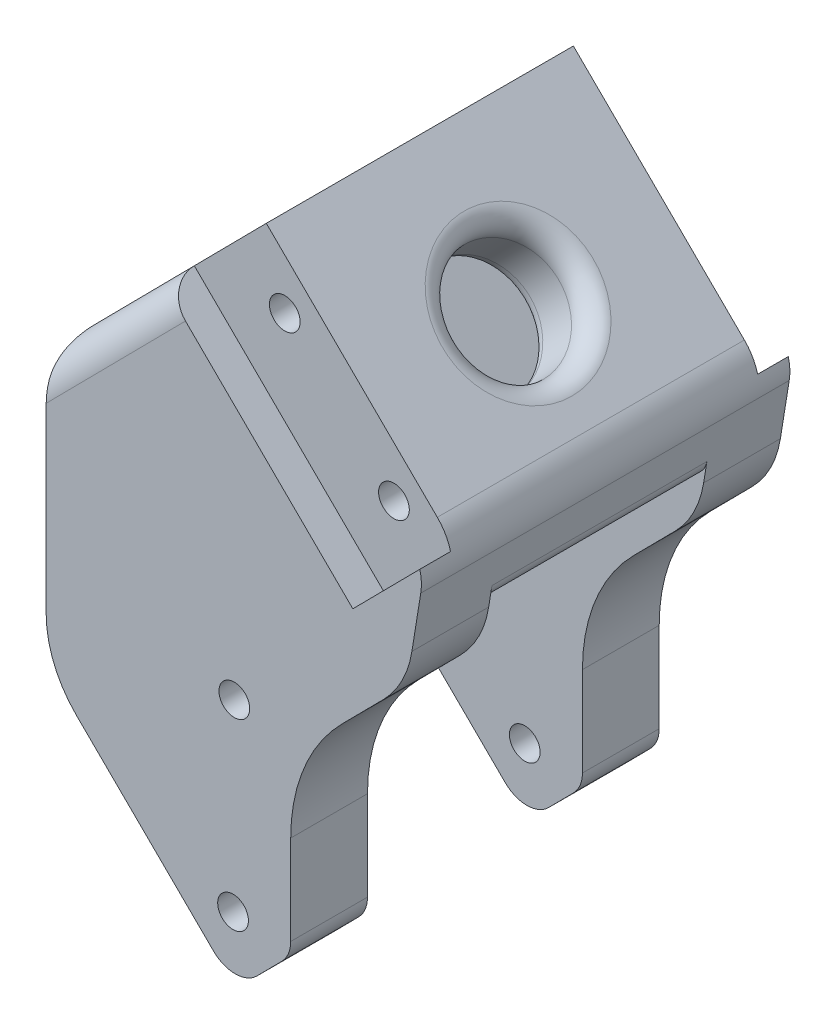
SolidWorks part; units mm, degrees
ref_plane "Front Plane" through (0, 0, 0) normal (0, 0, 1) x (1, 0, 0)
ref_plane "Top Plane" through (0, 0, 0) normal (0, 1, 0) x (1, 0, 0)
ref_plane "Right Plane" through (0, 0, 0) normal (1, 0, 0) x (0, 0, -1)
sketch "Sketch2" plane through (0, 0, 0) normal (0, 0, 1) x (1, 0, 0)
  line L2 (23.5277, -21.5779) -> (23.5277, 4.6943)
  line L3 (23.5277, 4.6943) -> (42.0332, 23.4086)
  line L4 (42.0332, 23.4086) -> (60.5208, 5.1273)
  line L5 (27.2641, -25) -> (27.2641, -13) construction
  line L10 (47.4183, -24.4139) -> (47.4183, -34.3953)
  line L11 (56.4972, -8.1393) -> (52.4057, -12.277)
  line L12 (54.8323, 10.7523) -> (170.8484, 128.0778) construction
  line L13 (42.0154, -39.8592) -> (23.5277, -21.5779)
  line L14 (42.0154, -39.8592) -> (47.4183, -34.3953)
  line L15 (60.5208, 5.1273) -> (59.2592, -2.6995)
  arc A2 (52.4057, -12.277) -> (47.4183, -24.4139) centre (64.6795, -24.4139) ccw
  arc A3 (59.2592, -2.6995) -> (56.4972, -8.1393) centre (49.3866, -1.108) cw
  spline S0 degree 3 poles (43.285, -33.4848) (43.3054, -30.4849) (40.3055, -30.4644) (40.285, -33.4643) (40.2646, -36.4643) (43.2645, -36.4848) (43.285, -33.4848) (43.3054, -30.4849) (40.3055, -30.4644) knots -0.5 0 0 0 0.5 0.5 0.5 1 1 1 1.5 1.5 1.5 weights 1 0.333333 0.333333 1 0.333333 0.333333 1 0.333333 0.333333 only from (43.285, -33.4848) to (43.285, -33.4848) construction
  spline S1 degree 3 poles (43.285, -33.4848) (43.3054, -30.4849) (40.3055, -30.4644) (40.285, -33.4643) (40.2646, -36.4643) (43.2645, -36.4848) (43.285, -33.4848) (43.3054, -30.4849) (40.3055, -30.4644) knots -0.5 0 0 0 0.5 0.5 0.5 1 1 1 1.5 1.5 1.5 weights 1 0.333333 0.333333 1 0.333333 0.333333 1 0.333333 0.333333 only from (43.285, -33.4848) to (43.285, -33.4848)
  spline S2 degree 3 poles (43.4078, -15.4852) (43.4283, -12.4853) (40.4284, -12.4648) (40.4079, -15.4648) (40.3874, -18.4647) (43.3873, -18.4852) (43.4078, -15.4852) (43.4283, -12.4853) (40.4284, -12.4648) knots -0.5 0 0 0 0.5 0.5 0.5 1 1 1 1.5 1.5 1.5 weights 1 0.333333 0.333333 1 0.333333 0.333333 1 0.333333 0.333333 only from (43.4078, -15.4852) to (43.4078, -15.4852) construction
  spline S3 degree 3 poles (43.4078, -15.4852) (43.4283, -12.4853) (40.4284, -12.4648) (40.4079, -15.4648) (40.3874, -18.4647) (43.3873, -18.4852) (43.4078, -15.4852) (43.4283, -12.4853) (40.4284, -12.4648) knots -0.5 0 0 0 0.5 0.5 0.5 1 1 1 1.5 1.5 1.5 weights 1 0.333333 0.333333 1 0.333333 0.333333 1 0.333333 0.333333 only from (43.4078, -15.4852) to (43.4078, -15.4852)
  dimension "D1" = 10
extrude "Boss-Extrude1" add sketch "Sketch2" along normal blind 8
sketch "Sketch3" plane through (0, 0, -20) normal (0, 0, -1) x (-1, 0, 0)
  line L5 (-47.4183, -24.4139) -> (-47.4183, -34.3953)
  line L7 (-47.4183, -24.4139) -> (-47.4183, -34.3953)
  line L8 (-23.5277, -21.5779) -> (-23.5277, 4.6943)
  line L9 (-23.5277, 4.6943) -> (-42.0332, 23.4086)
  line L10 (-42.0332, 23.4086) -> (-60.5208, 5.1273)
  line L14 (-23.5277, -21.5779) -> (-23.5277, 4.6943)
  line L15 (-23.5277, 4.6943) -> (-42.0332, 23.4086)
  line L16 (-42.0332, 23.4086) -> (-60.5208, 5.1273)
  line L18 (-56.4972, -8.1393) -> (-52.4057, -12.277)
  line L20 (-56.4972, -8.1393) -> (-52.4057, -12.277)
  line L23 (-47.4183, -34.3953) -> (-42.0154, -39.8592)
  line L24 (-47.4183, -34.3953) -> (-42.0154, -39.8592)
  line L25 (-42.0154, -39.8592) -> (-23.5277, -21.5779)
  line L26 (-42.0154, -39.8592) -> (-23.5277, -21.5779)
  line L28 (-60.5208, 5.1273) -> (-59.2592, -2.6995)
  line L29 (-60.5208, 5.1273) -> (-59.2592, -2.6995)
  arc A1 (-47.4183, -24.4139) -> (-52.4057, -12.277) centre (-64.6795, -24.4139) ccw
  arc A4 (-47.4183, -24.4139) -> (-52.4057, -12.277) centre (-64.6795, -24.4139) ccw
  arc A6 (-59.2592, -2.6995) -> (-56.4972, -8.1393) centre (-49.3866, -1.108) ccw
  arc A7 (-59.2592, -2.6995) -> (-56.4972, -8.1393) centre (-49.3866, -1.108) ccw
  dimension "D1" = 0
extrude "Boss-Extrude2" add sketch "Sketch3" along normal blind 8 separate body
sketch "Sketch4" plane through (0, 0, 8) normal (0, 0, 1) x (1, 0, 0)
  line L0 (59.2592, -2.6995) -> (60.5208, 5.1273) construction
  line L2 (60.5208, 5.1273) -> (42.0332, 23.4086)
  line L3 (42.0332, 23.4086) -> (36.4166, 17.7287)
  line L4 (59.2592, -2.6995) -> (60.5208, 5.1273)
  line L5 (58.8204, -4.4251) -> (36.4166, 17.7287)
  arc A0 (56.4972, -8.1393) -> (59.2592, -2.6995) centre (49.3866, -1.108) ccw construction
  arc A2 (58.8204, -4.4251) -> (59.2592, -2.6995) centre (49.3866, -1.108) ccw
extrude "Boss-Extrude3" add sketch "Sketch4" against normal up to surface (36 mm away) up to face at (45.385, -10.9855, -28)
fillet "Fillet3" radius 6 2 edges at (23.5277, 4.6943, -24) (23.5277, 4.6943, 4)
sketch "Sketch10" plane through (32.4843, 32.8509, 0) normal (0.7031, 0.7111, 0) x (0.7111, -0.7031, 0)
  line L0 (13.429, -8) -> (16.429, -8)
  line L1 (39.429, -8) -> (13.429, -8) construction
  line L2 (13.429, -8) -> (13.429, -5)
  line L3 (13.429, -8) -> (13.429, 28) construction
  line L4 (13.429, 10) -> (38.817, 10) construction
  line L6 (13.429, 28) -> (13.429, 25)
  line L7 (13.429, 28) -> (16.429, 28)
  arc A0 (16.429, -8) -> (13.429, -5) centre (16.429, -5) cw
  arc A1 (16.429, 28) -> (13.429, 25) centre (16.429, 25) ccw
extrude "Cut-Extrude3" cut sketch "Sketch10" against normal through all
sketch "Sketch12" plane through (0, 0, -20) normal (0, 0, 1) x (1, 0, 0)
  line L0 (25.2613, 6.4475) -> (36.4166, 17.7287) construction
  line L1 (29.4243, 10.6574) -> (36.4166, 17.7287)
  line L2 (25.2613, 6.4475) -> (42.0332, 23.4086) construction
  line L3 (36.4166, 17.7287) -> (40.0102, 14.2522)
  line L4 (40.0102, 14.2522) -> (33.0572, 7.065)
  line L5 (33.0572, 7.065) -> (29.4243, 10.6574)
extrude "Boss-Extrude5" add sketch "Sketch12" along normal up to surface (20 mm away) up to face at (41.19, -11.8148, 0)
sketch "Sketch13" plane through (0, 0, -20) normal (0, 0, 1) x (1, 0, 0)
  line L7 (39.9722, 14.2128) -> (33.0572, 7.065)
  line L8 (33.0572, 7.065) -> (29.4243, 10.6574)
  line L9 (29.4243, 10.6574) -> (25.2613, 6.4475)
  line L10 (23.5277, 2.2287) -> (23.5277, -21.5779)
  line L11 (23.5277, -21.5779) -> (42.0154, -39.8592)
  line L12 (23.5277, -21.5779) -> (42.0154, -39.8592)
  line L13 (58.8204, -4.4251) -> (39.9722, 14.2128)
  line L14 (39.9722, 14.2128) -> (33.0572, 7.065)
  line L16 (29.4243, 10.6574) -> (25.2613, 6.4475)
  line L17 (23.5277, 2.2287) -> (23.5277, -21.5779)
  line L20 (58.8204, -4.4251) -> (39.9722, 14.2128)
  line L21 (33.0572, 7.065) -> (29.4243, 10.6574)
  line L30 (52.4057, -12.277) -> (56.4972, -8.1393)
  line L31 (52.4057, -12.277) -> (56.4972, -8.1393)
  line L33 (42.0154, -39.8592) -> (47.4183, -34.3953)
  line L34 (42.0154, -39.8592) -> (47.4183, -34.3953)
  line L35 (47.4183, -34.3953) -> (47.4183, -24.4139)
  line L36 (47.4183, -34.3953) -> (47.4183, -24.4139)
  arc A3 (52.4057, -12.277) -> (47.4183, -24.4139) centre (64.6795, -24.4139) ccw
  arc A4 (25.2613, 6.4475) -> (23.5277, 2.2287) centre (29.5277, 2.2287) ccw
  arc A5 (52.4057, -12.277) -> (47.4183, -24.4139) centre (64.6795, -24.4139) ccw
  arc A8 (25.2613, 6.4475) -> (23.5277, 2.2287) centre (29.5277, 2.2287) ccw
  arc A13 (56.4972, -8.1393) -> (58.8204, -4.4251) centre (49.3866, -1.108) ccw
  arc A14 (56.4972, -8.1393) -> (58.8204, -4.4251) centre (49.3866, -1.108) ccw
  dimension "D1" = 0
extrude "Cut-Extrude5" cut sketch "Sketch13" against normal blind 0.5
sketch "Sketch14" plane through (0, 0, 0) normal (0, 0, -1) x (-1, 0, 0)
  line L7 (-25.2613, 6.4475) -> (-29.4243, 10.6574)
  line L8 (-29.4243, 10.6574) -> (-33.0572, 7.065)
  line L9 (-33.0572, 7.065) -> (-39.9722, 14.2128)
  line L10 (-39.9722, 14.2128) -> (-58.8204, -4.4251)
  line L12 (-47.4183, -24.4139) -> (-47.4183, -34.3953)
  line L13 (-23.5277, -21.5779) -> (-23.5277, 2.2287)
  line L14 (-25.2613, 6.4475) -> (-29.4243, 10.6574)
  line L16 (-33.0572, 7.065) -> (-39.9722, 14.2128)
  line L17 (-39.9722, 14.2128) -> (-58.8204, -4.4251)
  line L20 (-23.5277, -21.5779) -> (-23.5277, 2.2287)
  line L21 (-29.4243, 10.6574) -> (-33.0572, 7.065)
  line L27 (-47.4183, -24.4139) -> (-47.4183, -34.3953)
  line L30 (-56.4972, -8.1393) -> (-52.4057, -12.277)
  line L31 (-56.4972, -8.1393) -> (-52.4057, -12.277)
  line L33 (-47.4183, -34.3953) -> (-42.0154, -39.8592)
  line L34 (-47.4183, -34.3953) -> (-42.0154, -39.8592)
  line L35 (-42.0154, -39.8592) -> (-23.5277, -21.5779)
  line L36 (-42.0154, -39.8592) -> (-23.5277, -21.5779)
  arc A3 (-47.4183, -24.4139) -> (-52.4057, -12.277) centre (-64.6795, -24.4139) ccw
  arc A5 (-47.4183, -24.4139) -> (-52.4057, -12.277) centre (-64.6795, -24.4139) ccw
  arc A7 (-23.5277, 2.2287) -> (-25.2613, 6.4475) centre (-29.5277, 2.2287) ccw
  arc A11 (-23.5277, 2.2287) -> (-25.2613, 6.4475) centre (-29.5277, 2.2287) ccw
  arc A13 (-58.8204, -4.4251) -> (-56.4972, -8.1393) centre (-49.3866, -1.108) ccw
  arc A14 (-58.8204, -4.4251) -> (-56.4972, -8.1393) centre (-49.3866, -1.108) ccw
  dimension "D1" = 0
extrude "Cut-Extrude6" cut sketch "Sketch14" against normal blind 0.5
fillet "Fillet7" radius 10 2 edges at (23.5277, -21.5779, -24.25) (23.5277, -21.5779, 4.25)
sketch "Sketch16" plane through (0, 0, 8) normal (0, 0, 1) x (1, 0, 0)
  line L0 (53.4888, -1.9826) -> (35.0012, 16.2987)
  line L1 (35.0012, 16.2987) -> (42.3737, 23.7544)
  line L2 (42.3737, 23.7544) -> (60.8613, 5.4731)
  line L3 (53.4888, -1.9826) -> (183.5674, 129.5642) construction
  line L4 (60.8613, 5.4731) -> (53.4888, -1.9826)
extrude "Cut-Extrude8" cut sketch "Sketch16" against normal blind 3
sketch "Sketch18" plane through (0, 0, -28) normal (0, 0, -1) x (-1, 0, 0)
  line L4 (-35.0019, 16.298) -> (-42.0332, 23.4086)
  line L5 (-53.4888, -1.9826) -> (-35.0019, 16.298)
  line L6 (-60.5201, 5.128) -> (-53.4888, -1.9826)
  line L7 (-42.0332, 23.4086) -> (-60.5201, 5.128)
  line L8 (-35.0019, 16.298) -> (-42.0332, 23.4086)
  line L9 (-53.4888, -1.9826) -> (-35.0019, 16.298)
  line L10 (-60.5201, 5.128) -> (-53.4888, -1.9826)
  line L11 (-42.0332, 23.4086) -> (-60.5201, 5.128)
  dimension "D1" = 0
extrude "Cut-Extrude9" cut sketch "Sketch18" against normal blind 3
sketch "Sketch19" plane through (0, 0, 8) normal (0, 0, 1) x (1, 0, 0)
  spline S0 degree 3 poles (53.0038, 6.1549) (53.0038, 3.1549) (56.0038, 3.1549) (56.0038, 6.1549) (56.0038, 9.1549) (53.0038, 9.1549) (53.0038, 6.1549) (53.0038, 3.1549) (56.0038, 3.1549) knots -0.5 0 0 0 0.5 0.5 0.5 1 1 1 1.5 1.5 1.5 weights 1 0.333333 0.333333 1 0.333333 0.333333 1 0.333333 0.333333 only from (53.0038, 6.1549) to (53.0038, 6.1549) construction
  spline S1 degree 3 poles (53.0038, 6.1549) (53.0038, 3.1549) (56.0038, 3.1549) (56.0038, 6.1549) (56.0038, 9.1549) (53.0038, 9.1549) (53.0038, 6.1549) (53.0038, 3.1549) (56.0038, 3.1549) knots -0.5 0 0 0 0.5 0.5 0.5 1 1 1 1.5 1.5 1.5 weights 1 0.333333 0.333333 1 0.333333 0.333333 1 0.333333 0.333333 only from (53.0038, 6.1549) to (53.0038, 6.1549)
  spline S2 degree 3 poles (42.3379, 16.7019) (42.3379, 13.7019) (45.3379, 13.7019) (45.3379, 16.7019) (45.3379, 19.7019) (42.3379, 19.7019) (42.3379, 16.7019) (42.3379, 13.7019) (45.3379, 13.7019) knots -0.5 0 0 0 0.5 0.5 0.5 1 1 1 1.5 1.5 1.5 weights 1 0.333333 0.333333 1 0.333333 0.333333 1 0.333333 0.333333 only from (42.3379, 16.7019) to (42.3379, 16.7019) construction
  spline S3 degree 3 poles (42.3379, 16.7019) (42.3379, 13.7019) (45.3379, 13.7019) (45.3379, 16.7019) (45.3379, 19.7019) (42.3379, 19.7019) (42.3379, 16.7019) (42.3379, 13.7019) (45.3379, 13.7019) knots -0.5 0 0 0 0.5 0.5 0.5 1 1 1 1.5 1.5 1.5 weights 1 0.333333 0.333333 1 0.333333 0.333333 1 0.333333 0.333333 only from (42.3379, 16.7019) to (42.3379, 16.7019)
extrude "Cut-Extrude10" cut sketch "Sketch19" against normal up to surface (36 mm away) up to face at (45.2881, -10.8333, -28)
fillet "Fillet8" radius 3 4 edges at (42.0154, -39.8592, 4.25) (42.0154, -39.8592, -24.25) (47.4183, -34.3953, -24.25) (47.4183, -34.3953, 4.25)
sketch "Sketch20" plane through (0, 0, -28) normal (0, 0, -1) x (-1, 0, 0)
  circle A0 centre (-41.9079, -15.475) radius 1.5 construction
  circle A1 centre (-41.785, -33.4746) radius 1.5 construction
  circle A2 centre (-41.9079, -15.475) radius 1.5
  circle A3 centre (-41.785, -33.4746) radius 1.5
extrude "Cut-Extrude11" cut sketch "Sketch20" against normal up to surface (7.5 mm away) up to face at (39.4985, -13.0132, -20.5)
sketch "Sketch21" plane through (0, 0, -28) normal (0, 0, -1) x (-1, 0, 0)
  circle A0 centre (-41.9079, -15.475) radius 2.25
  circle A1 centre (-41.785, -33.4746) radius 2.25
extrude "Cut-Extrude12" cut sketch "Sketch21" against normal blind 3
sketch "Sketch22" plane through (0, 0, -28) normal (0, 0, -1) x (-1, 0, 0)
  line L0 (-59.2592, -2.6995) -> (-60.5208, 5.1273) construction
  line L1 (-42.0332, 23.4086) -> (-60.5201, 5.128) construction
  line L2 (-60.1226, 2.6568) -> (-60.5208, 5.1273)
  line L3 (-60.5208, 5.1273) -> (-58.7415, 6.8868)
  arc A0 (-60.1226, 2.6568) -> (-58.7415, 6.8868) centre (-55.3237, 3.4304) cw
extrude "Cut-Extrude13" cut sketch "Sketch22" against normal up to surface (36 mm away) up to face at (45.1668, -14.0968, 8)
fillet "Fillet9" radius 2 3 edges at (33.0572, 7.065, -10) (29.4243, 10.6574, -10) (58.8204, -4.4251, -10)
sketch "Sketch24" plane through (32.4843, 32.8509, 0) normal (0.7031, 0.7111, 0) x (0.7111, -0.7031, 0)
  arc A0 (25.1591, 15.1019) -> (28.6973, 15.1019) centre (26.9281, 9.9999) ccw construction
  circle A1 centre (26.9281, 9.9999) radius 5.4
extrude "Cut-Extrude15" cut sketch "Sketch24" against normal up to surface (7.9879 mm away) up to face at (48.0843, 6.1913, -10)
fillet "Fillet12" radius 2 2 edges at (47.7922, 17.7139, -9.9999) (49.8551, 4.4402, -9.9999)
